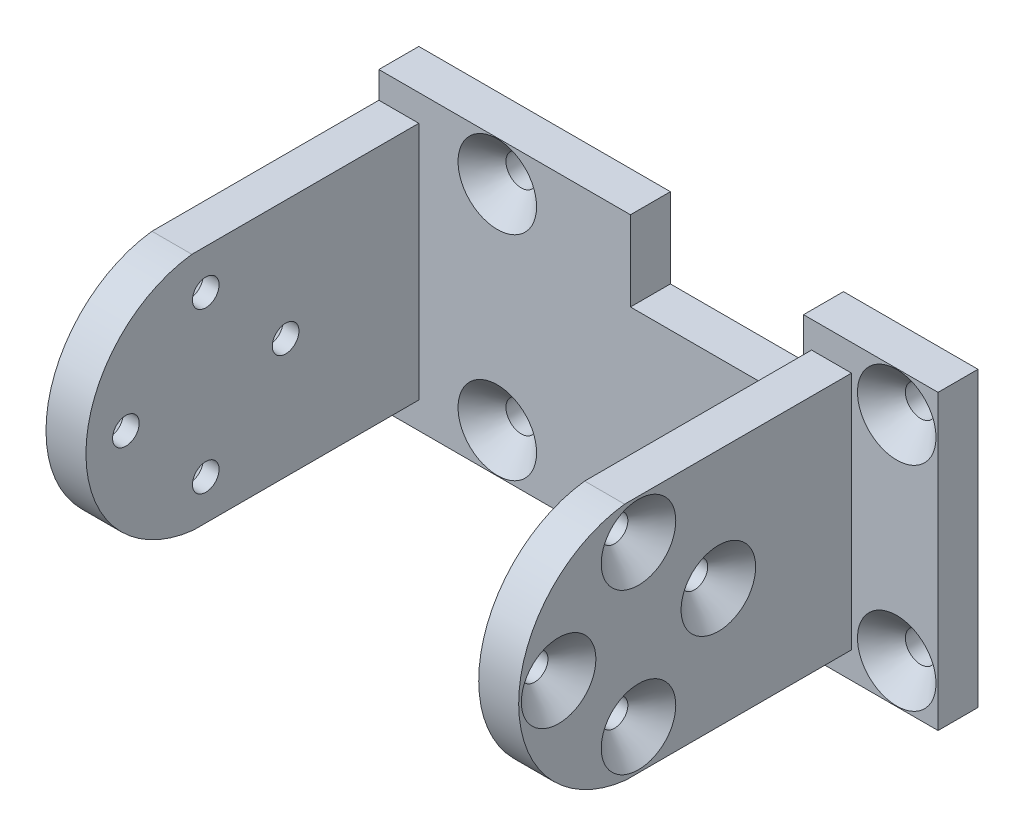
SolidWorks part; units mm, degrees
ref_plane "Front Plane" through (0, 0, 0) normal (0, 0, 1) x (1, 0, 0)
ref_plane "Top Plane" through (0, 0, 0) normal (0, 1, 0) x (1, 0, 0)
ref_plane "Right Plane" through (0, 0, 0) normal (1, 0, 0) x (0, 0, -1)
ref_plane "Plane1" through (0, 0, 47.8926) normal (0, 0, 1) x (1, 0, 0)
sketch "Sketch1" plane through (0, 0, 47.8926) normal (0, 0, 1) x (1, 0, 0)
  line L0 (29.75, 233.2226) -> (-12.25, 233.2226)
  line L1 (-12.25, 233.2226) -> (-12.25, 211.2226)
  line L2 (-12.25, 211.2226) -> (29.75, 211.2226)
  line L3 (29.75, 211.2226) -> (29.75, 233.2226)
extrude "Boss-Extrude1" add sketch "Sketch1" against normal blind 3
sketch "Sketch2" plane through (0, 0, 44.8926) normal (0, 0, -1) x (-1, 0, 0)
  line L0 (-6.6467, 233.2226) -> (-19.6467, 233.2226)
  line L1 (-19.6467, 233.2226) -> (-19.6467, 227.2226)
  line L2 (-19.6467, 227.2226) -> (-6.6467, 227.2226)
  line L3 (-6.6467, 227.2226) -> (-6.6467, 233.2226)
extrude "Cut-Extrude1" cut sketch "Sketch2" against normal through all
sketch "Sketch3" plane through (0, 0, 44.8926) normal (0, 0, -1) x (-1, 0, 0)
  line L0 (-19.6467, 211.2226) -> (-6.6467, 211.2226)
  line L1 (-6.6467, 211.2226) -> (-6.6467, 217.2226)
  line L2 (-6.6467, 217.2226) -> (-19.6467, 217.2226)
  line L3 (-19.6467, 217.2226) -> (-19.6467, 211.2226)
extrude "Cut-Extrude2" cut sketch "Sketch3" against normal through all
ref_plane "Plane2" through (-12.25, 0, 0) normal (-1, 0, 0) x (0, -1, 0)
sketch "Sketch4" plane through (-12.25, 0, 0) normal (-1, 0, 0) x (0, -1, 0)
  line L0 (-231.2226, 64.9357) -> (-231.2226, 47.8926)
  line L1 (-231.2226, 47.8926) -> (-213.2226, 47.8926)
  line L2 (-213.2226, 47.8926) -> (-213.2226, 64.8395)
  arc A0 (-213.2226, 64.8395) -> (-231.2226, 64.9357) centre (-222.2283, 63.8306) ccw
extrude "Boss-Extrude2" add sketch "Sketch4" against normal blind 3
ref_plane "Plane3" through (23.25, 0, 0) normal (1, 0, 0) x (0, 0, -1)
sketch "Sketch5" plane through (23.25, 0, 0) normal (1, 0, 0) x (0, 0, -1)
  line L0 (-64.8395, 213.2226) -> (-47.8926, 213.2226)
  line L1 (-47.8926, 213.2226) -> (-47.8926, 231.2226)
  line L2 (-47.8926, 231.2226) -> (-64.9357, 231.2226)
  arc A0 (-64.9357, 231.2226) -> (-64.8395, 213.2226) centre (-63.8306, 222.2283) ccw
extrude "Boss-Extrude3" add sketch "Sketch5" against normal blind 3
hole_wizard "Ø2.0 (2) Diameter Hole1" positions "Sketch7" profile "Sketch6" hole size "Ø2.0" standard "ANSI Metric"
sketch "Sketch7" plane through (23.25, 0, 0) normal (1, 0, 0) x (0, 0, -1)
  point P0 (-63.8928, 228.2222)
  point P1 (-69.8926, 222.2224)
  point P2 (-63.8928, 216.2226)
  point P3 (-57.893, 222.2224)
sketch "Sketch6" plane through (23.25, 228.2222, 63.8928) normal (0, 1, 0) x (0, 0, -1)
  line L0 (0, 0) -> (0, 3)
  line L1 (0, 3) -> (1, 3)
  line L2 (1, 3) -> (1, 1.8)
  line L3 (1, 1.8) -> (2.8, 0)
  line L5 (2.8, 0) -> (0, 0)
  line L6 (-1, 1.8) -> (-2.8, 0) construction
  line L11 (0, -6.35) -> (0, 107.95) construction
  dimension "Thru Hole Dia." = 2
  dimension "Thru Hole Depth" = 3
  dimension "Near C'Sink Dia." = 5.6
  dimension "Near C'Sink Angle" = 90
hole_wizard "CSK for M2 Flat Head Machine Screw1" positions "Sketch9" profile "Sketch8" countersink size "M2" standard "ANSI Metric"
sketch "Sketch9" plane through (0, 0, 47.8926) normal (0, 0, 1) x (1, 0, 0)
  point P0 (-3.3533, 230.215)
  point P1 (-3.3533, 214.215)
  point P2 (26.6467, 214.215)
  point P3 (26.6467, 230.215)
sketch "Sketch8" plane through (-3.3533, 230.215, 47.8926) normal (1, 0, 0) x (0, -1, 0)
  line L0 (0, 0) -> (0, 3)
  line L1 (0, 3) -> (1.15, 3)
  line L2 (1.15, 3) -> (1.15, 1.8)
  line L3 (1.15, 1.8) -> (2.95, 0)
  line L5 (2.95, 0) -> (0, 0)
  line L6 (-1.15, 1.8) -> (-2.95, 0) construction
  line L11 (0, -6.35) -> (0, 107.95) construction
  dimension "Thru Hole Dia." = 2.3
  dimension "Thru Hole Depth" = 3
  dimension "Near C'Sink Dia." = 5.9
  dimension "Near C'Sink Angle" = 90
hole_wizard "Ø2.0 (2) Diameter Hole2" positions "Sketch11" profile "Sketch10" hole size "Ø2.0" standard "ANSI Metric"
sketch "Sketch11" plane through (-12.25, 0, 0) normal (-1, 0, 0) x (0, 0, 1)
  point P0 (63.8928, 228.2222)
  point P1 (69.8926, 222.2224)
  point P2 (63.8928, 216.2226)
  point P3 (57.893, 222.2224)
sketch "Sketch10" plane through (-12.25, 228.2222, 63.8928) normal (0, 1, 0) x (0, 0, 1)
  line L0 (0, 0) -> (0, 42)
  line L1 (0, 42) -> (1, 42)
  line L2 (1, 42) -> (1, 1.8)
  line L3 (1, 1.8) -> (2.8, 0)
  line L5 (2.8, 0) -> (0, 0)
  line L6 (-1, 1.8) -> (-2.8, 0) construction
  line L11 (0, -6.35) -> (0, 107.95) construction
  dimension "Thru Hole Dia." = 2
  dimension "Thru Hole Depth" = 42
  dimension "Near C'Sink Dia." = 5.6
  dimension "Near C'Sink Angle" = 90
